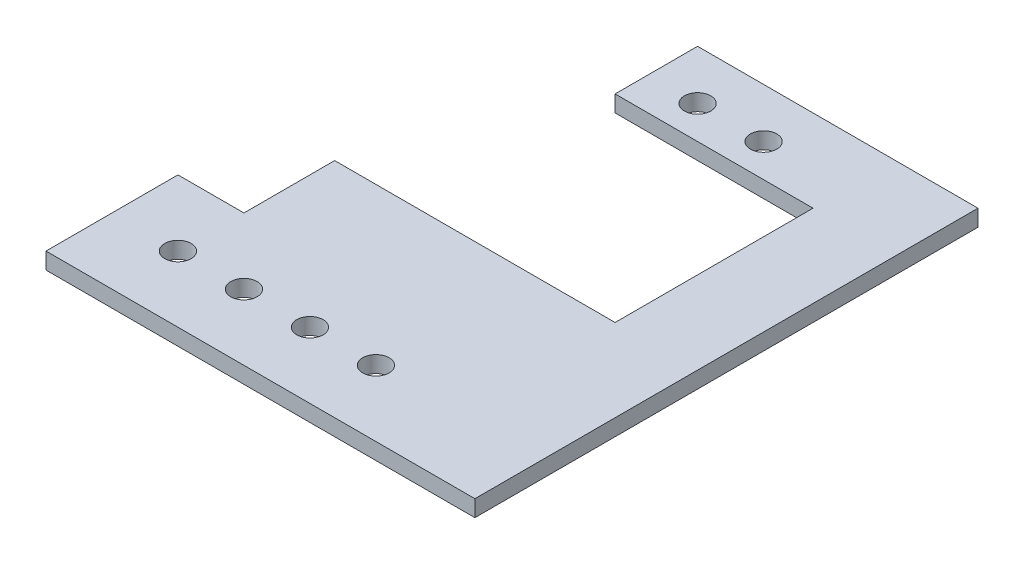
SolidWorks part; units mm, degrees
material "Cast Carbon Steel"
ref_plane "Front Plane" through (0, 0, 0) normal (0, 0, 1) x (1, 0, 0)
ref_plane "Top Plane" through (0, 0, 0) normal (0, 1, 0) x (1, 0, 0)
ref_plane "Right Plane" through (0, 0, 0) normal (1, 0, 0) x (0, 0, -1)
other "Configuration Table"
sketch "Sketch1" plane through (0, 0, 0) normal (0, 1, 0) x (1, 0, 0)
  line L1 (0, 0) -> (82.55, 0)
  line L2 (0, 0) -> (0, 96.8375)
  line L3 (0, 96.8375) -> (82.55, 96.8375)
  line L4 (82.55, 0) -> (82.55, 96.8375)
  line L5 (28.575, 42.8625) -> (66.675, 42.8625)
  line L6 (28.575, 42.8625) -> (28.575, 80.9625)
  line L7 (28.575, 80.9625) -> (66.675, 80.9625)
  line L8 (66.675, 42.8625) -> (66.675, 80.9625)
  dimension "D1" = 82.55
  dimension "D2" = 96.8375
  dimension "D3" = 38.1
  dimension "D4" = 42.8625
  dimension "D5" = 28.575
  dimension "D6" = 15.875
  dimension "D7" = 15.875
base flange "Base-Flange2" sketch "Sketch1" thickness 3.175 reverse thickness direction no parameters "D1"=0.7366
sketch "Sketch3" plane through (0, 0, 0) normal (0, 1, 0) x (1, 0, 0)
  line L5 (0, 0) -> (82.55, 0) construction
  line L6 (0, 96.8375) -> (12.7, 96.8375)
  line L7 (0, 96.8375) -> (0, 25.4)
  line L8 (0, 25.4) -> (12.7, 25.4)
  line L9 (12.7, 96.8375) -> (12.7, 25.4)
  dimension "D1" = 25.4
  dimension "D2" = 12.7
extrude "Cut-Extrude2" cut sketch "Sketch3" against normal through all normal cut yes
sketch "Sketch2" plane through (0, 0, 0) normal (0, 1, 0) x (1, 0, 0)
  line L0 (0, 25.4) -> (0, 0) construction
  line L1 (0, 0) -> (82.55, 0) construction
  circle A0 centre (12.7, 12.7) radius 2.54
  circle A4 centre (25.4, 12.7) radius 2.54
  circle A5 centre (38.1, 12.7) radius 2.54
  circle A6 centre (50.8, 12.7) radius 2.54
  dimension "D1" = 5.08
  dimension "D2" = 12.7
  dimension "D3" = 12.7
  dimension "D5" = 50.8
  dimension "D4" = 4
extrude "Cut-Extrude1" cut sketch "Sketch2" against normal through all normal cut yes
sketch "Sketch5" plane through (0, 0, 0) normal (0, 1, 0) x (1, 0, 0)
  line L0 (12.7, 25.4) -> (12.7, 96.8375) construction
  line L1 (12.7, 42.8625) -> (28.575, 42.8625)
  line L2 (12.7, 42.8625) -> (12.7, 96.8375)
  line L3 (12.7, 96.8375) -> (28.575, 96.8375)
  line L4 (28.575, 42.8625) -> (28.575, 96.8375)
  line L5 (82.55, 96.8375) -> (12.7, 96.8375) construction
  line L7 (28.575, 42.8625) -> (66.675, 42.8625) construction
  point P8 (28.575, 42.8625)
  dimension "D1" = 15.875
extrude "Cut-Extrude6" cut sketch "Sketch5" against normal through all normal cut yes
sketch "Sketch6" plane through (0, 0, 0) normal (0, 1, 0) x (1, 0, 0)
  line L1 (82.55, 96.8375) -> (60.325, 96.8375)
  line L2 (82.55, 96.8375) -> (82.55, 42.8625)
  line L3 (82.55, 42.8625) -> (60.325, 42.8625)
  line L4 (60.325, 96.8375) -> (60.325, 42.8625)
  dimension "D1" = 22.225
extrude "Cut-Extrude5" [suppressed] cut sketch "Sketch6" against normal through all
sketch "Sketch7" plane through (0, 0, 0) normal (0, 1, 0) x (1, 0, 0)
  line L1 (0, 25.4) -> (0, 0) construction
  line L2 (0, 0) -> (82.55, 0) construction
  circle A0 centre (38.1, 87.3125) radius 2.54
  circle A1 centre (38.1, 12.7) radius 2.54 construction
  circle A2 centre (50.8, 87.3125) radius 2.54
  point P10 (0, 0)
  dimension "D1" = 38.1
  dimension "D2" = 87.3125
  dimension "D3" = 12.7
extrude "Cut-Extrude7" cut sketch "Sketch7" against normal through all normal cut yes
sketch "Bend-Lines3" [suppressed] plane through (0, 0, 0) normal (0, 1, 0) x (1, 0, 0)
sketch "Bounding-Box3" [suppressed] plane through (0, 0, 0) normal (0, 1, 0) x (1, 0, 0)
sheet metal parameters "Sheet-Metal2" thickness 3.175 parameters "D1"=0.7366
flat pattern "Flat-Pattern2" [suppressed]
sketch "Bend-Lines4" plane through (0, 0, 0) normal (0, 1, 0) x (1, 0, 0)
sketch3d "Bounding-Box4" [suppressed]
  line L0 (0, 0, 0) -> (0, 101.6, 0) construction
  line L1 (92.075, 0, 0) -> (92.075, 101.6, 0) construction
  line L2 (0, 0, 0) -> (92.075, 0, 0) construction
  line L3 (0, 101.6, 0) -> (92.075, 101.6, 0) construction
sheet metal parameters "Sheet-Metal3" thickness 3.175 parameters "D1"=0.7366
flat pattern "Flat-Pattern2"
sketch "Bend-Lines4" plane through (0, 0, 0) normal (0, 1, 0) x (1, 0, 0)
sketch3d "Bounding-Box4" [suppressed]
  line L0 (0, 0, 0) -> (0, 87.3125, 0) construction
  line L1 (73.025, 0, 0) -> (73.025, 87.3125, 0) construction
  line L2 (0, 0, 0) -> (73.025, 0, 0) construction
  line L3 (0, 87.3125, 0) -> (73.025, 87.3125, 0) construction
sheet metal parameters "Sheet-Metal4" thickness 3.175 parameters "D1"=0.7366
flat pattern "Flat-Pattern2"
sketch "Bend-Lines4" plane through (0, 0, 0) normal (0, 1, 0) x (1, 0, 0)
sketch3d "Bounding-Box4" [suppressed]
  line L0 (0, 0, 0) -> (0, 101.6, 0) construction
  line L1 (92.075, 0, 0) -> (92.075, 101.6, 0) construction
  line L2 (0, 0, 0) -> (92.075, 0, 0) construction
  line L3 (0, 101.6, 0) -> (92.075, 101.6, 0) construction
sheet metal parameters "Sheet-Metal7" thickness 3.175 parameters "D1"=0.7366
flat pattern "Flat-Pattern2"
sketch "Bend-Lines4" plane through (0, 0, 0) normal (0, 1, 0) x (1, 0, 0)
sketch3d "Bounding-Box4" [suppressed]
  line L0 (0, 0, 0) -> (0, 87.3125, 0) construction
  line L1 (73.025, 0, 0) -> (73.025, 87.3125, 0) construction
  line L2 (0, 0, 0) -> (73.025, 0, 0) construction
  line L3 (0, 87.3125, 0) -> (73.025, 87.3125, 0) construction
sheet metal parameters "Sheet-Metal9" thickness 3.175 parameters "D1"=0.7366
flat pattern "Flat-Pattern9"
sketch "Bend-Lines5" plane through (0, 0, 0) normal (0, 1, 0) x (1, 0, 0)
sketch3d "Bounding-Box5" [suppressed]
  line L0 (53.975, 87.3125, 0) -> (41.275, 87.3125, 0) construction
  line L1 (53.975, 80.9625, 0) -> (41.275, 80.9625, 0) construction
  line L2 (53.975, 87.3125, 0) -> (53.975, 80.9625, 0) construction
  line L3 (41.275, 87.3125, 0) -> (41.275, 80.9625, 0) construction
sheet metal parameters "Sheet-Metal10" thickness 3.175 parameters "D1"=0.7366
flat pattern "Flat-Pattern10"
sketch "Bend-Lines6" plane through (0, 0, 0) normal (0, 1, 0) x (1, 0, 0)
sketch3d "Bounding-Box6" [suppressed]
  line L0 (73.025, 42.8625, 0) -> (0, 42.8625, 0) construction
  line L1 (73.025, 0, 0) -> (0, 0, 0) construction
  line L2 (73.025, 42.8625, 0) -> (73.025, 0, 0) construction
  line L3 (0, 42.8625, 0) -> (0, 0, 0) construction
sheet metal parameters "Sheet-Metal11" thickness 3.175 parameters "D1"=0.7366
flat pattern "Flat-Pattern2"
sketch "Bend-Lines4" plane through (0, 0, 0) normal (0, 1, 0) x (1, 0, 0)
sketch3d "Bounding-Box4" [suppressed]
  line L0 (0, 0, 0) -> (0, 87.3125, 0) construction
  line L1 (73.025, 0, 0) -> (73.025, 87.3125, 0) construction
  line L2 (0, 0, 0) -> (73.025, 0, 0) construction
  line L3 (0, 87.3125, 0) -> (73.025, 87.3125, 0) construction
sheet metal parameters "Sheet-Metal12" thickness 3.175 parameters "D1"=0.7366
flat pattern "Flat-Pattern2"
sketch "Bend-Lines4" plane through (0, 0, 0) normal (0, 1, 0) x (1, 0, 0)
sketch3d "Bounding-Box4" [suppressed]
  line L0 (0, 0, 0) -> (0, 96.8375, 0) construction
  line L1 (82.55, 0, 0) -> (82.55, 96.8375, 0) construction
  line L2 (0, 0, 0) -> (82.55, 0, 0) construction
  line L3 (0, 96.8375, 0) -> (82.55, 96.8375, 0) construction
sheet metal parameters "Sheet-Metal14" thickness 3.175 parameters "D1"=0.7366
flat pattern "Flat-Pattern2"
sketch "Bend-Lines4" plane through (0, 0, 0) normal (0, 1, 0) x (1, 0, 0)
sketch3d "Bounding-Box4" [suppressed]
  line L0 (0, 0, 0) -> (0, 93.6625, 0) construction
  line L1 (79.375, 0, 0) -> (79.375, 93.6625, 0) construction
  line L2 (0, 0, 0) -> (79.375, 0, 0) construction
  line L3 (0, 93.6625, 0) -> (79.375, 93.6625, 0) construction
